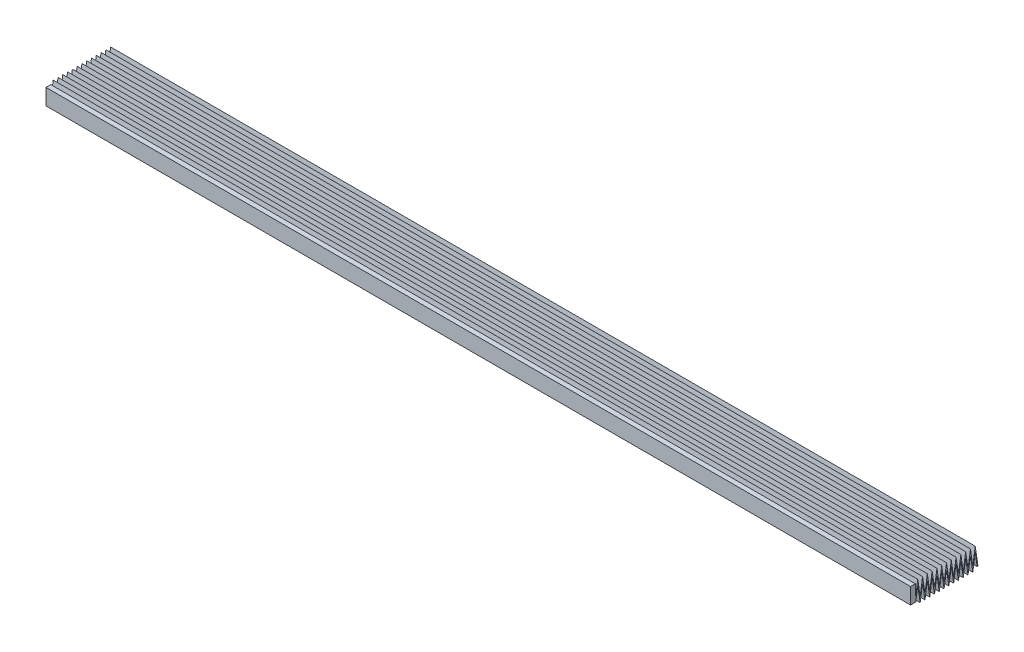
SolidWorks part; units mm, degrees
ref_plane "Front Plane" through (0, 0, 0) normal (0, 0, 1) x (1, 0, 0)
ref_plane "Top Plane" through (0, 0, 0) normal (0, 1, 0) x (1, 0, 0)
ref_plane "Right Plane" through (0, 0, 0) normal (1, 0, 0) x (0, 0, -1)
sketch "Sketch2" plane through (0, 0, 0) normal (0, 0, 1) x (1, 0, 0)
  line L1 (-270, 10) -> (270, 10)
  line L2 (-270, 10) -> (-270, 0)
  line L3 (-270, 0) -> (270, 0)
  line L4 (270, 10) -> (270, 0)
  point P4 (0, 0)
  dimension "D1" = 10
  dimension "D2" = 540
extrude "Boss-Extrude1" add sketch "Sketch2" along normal blind 3
sketch "Sketch3" plane through (270, 0, 0) normal (1, 0, 0) x (0, 0, -1)
  line L0 (0, 10) -> (38.8599, 10) construction
  line L1 (0, 0) -> (38.8599, 0) construction
  line L3 (0, 0) -> (1.4946, 10)
  line L4 (1.4946, 10) -> (2.9892, 0)
  line L5 (2.9892, 0) -> (4.4838, 10)
  line L6 (4.4838, 10) -> (5.9784, 0)
  line L7 (5.9784, 0) -> (7.4731, 10)
  line L8 (7.4731, 10) -> (8.9677, 0)
  line L9 (8.9677, 0) -> (10.4623, 10)
  line L10 (10.4623, 10) -> (11.9569, 0)
  line L11 (11.9569, 0) -> (13.4515, 10)
  line L12 (13.4515, 10) -> (14.9461, 0)
  line L13 (14.9461, 0) -> (16.4407, 10)
  line L14 (16.4407, 10) -> (17.9353, 0)
  line L15 (17.9353, 0) -> (19.4299, 10)
  line L16 (19.4299, 10) -> (20.9246, 0)
  line L17 (20.9246, 0) -> (22.4192, 10)
  line L18 (22.4192, 10) -> (23.9138, 0)
  line L20 (23.9138, 0) -> (25.4084, 10)
  line L21 (25.4084, 10) -> (26.903, 0)
  line L22 (26.903, 0) -> (28.3976, 10)
  line L23 (28.3976, 10) -> (29.8922, 0)
  line L24 (29.8922, 0) -> (31.3868, 10)
  line L25 (31.3868, 10) -> (32.8814, 0)
  line L26 (32.8814, 0) -> (34.376, 10)
  line L27 (34.376, 10) -> (35.8707, 0)
  line L28 (35.8707, 0) -> (37.3653, 10)
  line L29 (37.3653, 10) -> (38.8599, 0)
  line L30 (38.8599, 10) -> (38.8599, 0) construction
  line L32 (38.8599, 10) -> (38.8599, 0) construction
extrude "Extrude-Thin1" add sketch "Sketch3" against normal through all thin thin type mid plane wall 0.5
